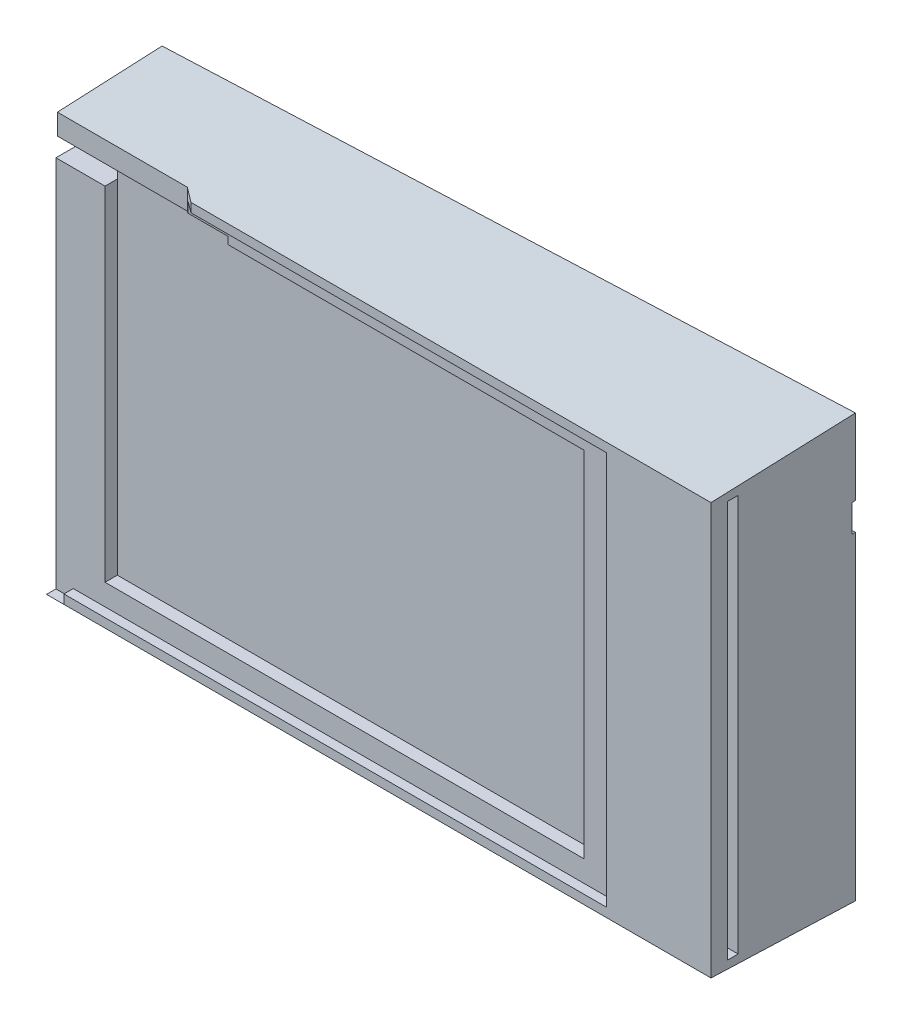
SolidWorks part; units mm, degrees
ref_plane "Front Plane" through (0, 0, 0) normal (0, 0, 1) x (1, 0, 0)
ref_plane "Top Plane" through (0, 0, 0) normal (0, 1, 0) x (1, 0, 0)
ref_plane "Right Plane" through (0, 0, 0) normal (1, 0, 0) x (0, 0, -1)
sketch "Sketch1" plane through (0, 0, 0) normal (0, 0, 1) x (1, 0, 0)
  line L1 (0, 0) -> (92, 0)
  line L2 (0, 0) -> (0, 61)
  line L3 (0, 61) -> (92, 61)
  line L4 (92, 0) -> (92, 61)
  dimension "D1" = 61
  dimension "D2" = 92
ref_plane "Plane1" through (92, 0, 0) normal (1, 0, 0) x (0, 0, -1)
sketch "Sketch2" plane through (92, 0, 0) normal (1, 0, 0) x (0, 0, -1)
  line L1 (0, 61) -> (20, 61.75)
  line L2 (0, 61) -> (0, 4)
  line L3 (0, 4) -> (20, 3.25)
  line L4 (20, 61.75) -> (20, 3.25)
  dimension "D1" = 20
  dimension "D2" = 57
  dimension "D3" = 58.5
ref_plane "Plane2" through (0, 0, 0) normal (1, 0, 0) x (0, 0, -1)
sketch "Sketch3" plane through (0, 0, 0) normal (1, 0, 0) x (0, 0, -1)
  line L1 (0, 61) -> (16, 61.75)
  line L2 (0, 61) -> (0, 4)
  line L3 (0, 4) -> (16, 3.25)
  line L4 (16, 61.75) -> (16, 3.25)
  dimension "D1" = 16
  dimension "D2" = 58.5
  dimension "D3" = 57
ref_plane "Plane3" through (0, 61, 0) normal (0, 1, 0) x (1, 0, 0)
loft "body" add profiles "Sketch3", "Sketch2" connector at (0, 61.75, -16) connector at (92, 61.75, -20)
sketch "Sketch5" plane through (0, 61, 0) normal (0, 1, 0) x (1, 0, 0)
  line L0 (0, 1.5) -> (18, 1.5)
  line L1 (0, -33.55) -> (0, 33.55) construction
  line L2 (18, 1.5) -> (20, 0)
  line L3 (0, 0) -> (92, 0) construction
  line L4 (0, 1.5) -> (0, 0)
  line L5 (0, 0) -> (20, 0)
  dimension "D1" = 1.5
  dimension "D2" = 20
  dimension "D3" = 2
sketch "Sketch6" plane through (0, 0, 0) normal (0, 0, 1) x (1, 0, 0)
  line L0 (23.8, 57.2) -> (23.8, 58.2)
  line L1 (6.8, 8.2) -> (73.1, 8.2)
  line L2 (6.8, 8.2) -> (6.8, 57.2)
  line L3 (6.8, 57.2) -> (73.1, 57.2)
  line L4 (73.1, 8.2) -> (73.1, 57.2)
  line L5 (6.8, 8.2) -> (73.1, 57.2) construction
  line L6 (6.8, 57.2) -> (73.1, 8.2) construction
  line L7 (23.8, 58.2) -> (6.8, 58.2)
  line L9 (0, 61) -> (92, 61) construction
  line L10 (0, 0) -> (0, 61) construction
  line L11 (6.8, 57.2) -> (6.8, 58.2)
  line L12 (6.8, 58.2) -> (6.8, 57.2)
  point P0 (39.95, 32.7)
  dimension "D1" = 66.3
  dimension "D2" = 49
  dimension "D3" = 1
  dimension "D4" = 17
  dimension "D5" = 3.8
  dimension "D6" = 6.8
extrude "film plane" cut sketch "Sketch6" against normal blind 3 contours L11 L3 L0 L7 | L1 L4 L3 L2 region at (15.3, 57.7, 0) region at (39.95, 32.7, 0)
sketch "Sketch7" plane through (0, 0, 0) normal (0, 0, 1) x (1, 0, 0)
  line L0 (0, 0) -> (0, 61) construction
  line L1 (77.5, 59.75) -> (0, 59.75)
  line L2 (77.5, 59.75) -> (77.5, 5.25)
  line L3 (77.5, 5.25) -> (0, 5.25)
  line L4 (0, 59.75) -> (0, 5.25)
  line L5 (92, 0) -> (92, 61) construction
  line L6 (77.5, 5.25) -> (77.5, 4) construction
  line L7 (0, 4) -> (92, 4) construction
  line L8 (77.5, 59.75) -> (77.5, 61) construction
  line L9 (0, 61) -> (92, 61) construction
  line L10 (2.4, 5.25) -> (2.4, 4)
  line L11 (2.4, 4) -> (0, 4)
  line L12 (0, 4) -> (0, 5.25)
  line M5 (0, 4) -> (92, 4)
  dimension "D1" = 54.5
  dimension "D2" = 14.5
  dimension "D3" = 2.4
extrude "Cut-Extrude2" cut sketch "Sketch7" against normal blind 1.3 contours L10 L3 M5 | L3 L2 L1 L4 region at (1.2, 4.625, 0)
sketch "notch" plane through (0, 0, -1.3) normal (0, 0, 1) x (1, 0, 0)
  line L0 (6.8, 58.2) -> (0, 58.2)
  line L1 (0, 59.75) -> (0, 4) construction
  line L2 (0, 58.2) -> (0, 55.7)
  line L3 (0, 55.7) -> (6.8, 55.7)
  line L4 (6.8, 58.2) -> (6.8, 8.2) construction
  line L5 (6.8, 55.7) -> (6.8, 58.2)
  dimension "D1" = 2.5
extrude "notch-cut" cut sketch "notch" against normal blind 4.1
sketch "Sketch10" plane through (-0.6943, 0, -15.9698) normal (-0.0434, 0, -0.9991) x (-0.9991, 0, 0.0434)
  line L0 (-92.7819, 51.25) -> (-86.4841, 51.25)
  line L1 (-92.7819, 3.25) -> (-92.7819, 61.75) construction
  line L2 (-86.4841, 51.25) -> (-86.4841, 47.45)
  line L3 (-86.4841, 47.45) -> (-92.7819, 47.45)
  line L4 (-92.7819, 47.45) -> (-92.7819, 51.25)
  line L6 (-92.7819, 61.75) -> (-0.695, 61.75) construction
  dimension "D1" = 10.5
  dimension "D2" = 3.8
extrude "Cut-Extrude4" cut sketch "Sketch10" against normal blind 0.5
sketch "Sketch11" plane through (-0.6943, 0, -15.9698) normal (-0.0434, 0, -0.9991) x (-0.9991, 0, 0.0434)
  line L0 (-92.7819, 3.25) -> (-92.7819, 47.45) construction
  line L1 (-72.5, 14.5) -> (-64, 14.5)
  line L2 (-75, 17) -> (-75, 48)
  line L3 (-72.5, 50.5) -> (-64, 50.5)
  line L4 (-61.5, 17) -> (-61.5, 48)
  line L5 (-24.5, 14.5) -> (-16, 14.5)
  line L6 (-27, 17) -> (-27, 48)
  line L7 (-24.5, 50.5) -> (-16, 50.5)
  line L8 (-13.5, 17) -> (-13.5, 48)
  line L11 (-0.695, 32.5) -> (-92.7819, 32.5) construction
  line L12 (-0.695, 3.25) -> (-0.695, 61.75) construction
  line L13 (0, 0) -> (0, 61) construction
  arc A0 (-24.5, 14.5) -> (-27, 17) centre (-24.5, 17) cw
  arc A1 (-16, 14.5) -> (-13.5, 17) centre (-16, 17) ccw
  arc A2 (-16, 50.5) -> (-13.5, 48) centre (-16, 48) cw
  arc A3 (-27, 48) -> (-24.5, 50.5) centre (-24.5, 48) cw
  arc A4 (-75, 48) -> (-72.5, 50.5) centre (-72.5, 48) cw
  arc A5 (-64, 50.5) -> (-61.5, 48) centre (-64, 48) cw
  arc A6 (-64, 14.5) -> (-61.5, 17) centre (-64, 17) ccw
  arc A7 (-72.5, 14.5) -> (-75, 17) centre (-72.5, 17) cw
  point P10 (-13.5, 32.5)
  point P27 (-75, 50.5)
  point P34 (-75, 14.5)
  dimension "D6" = 2.5
  dimension "D1" = 36
  dimension "D3" = 34.5
  dimension "D4" = 13.5
  dimension "D2" = 13.5
  dimension "D5" = 13.5
extrude "Cut-Extrude5" cut sketch "Sketch11" against normal blind 1.5
extrude "Cut-Extrude6" cut sketch "Sketch5" against normal blind 5 and the other way through all
sketch "草图1" plane through (92, 0, 0) normal (1, 0, 0) x (0, 0, -1)
  line L0 (3, 60) -> (3, 5)
  line L1 (0, 61) -> (0, 4) construction
  point P4 (3, 5.3153)
  point P5 (0, 32.5)
  point P6 (3, 32.5)
  dimension "D1" = 3
  dimension "D2" = 55
extrude "outlet" cut sketch "草图1" against normal blind 2 thin thin type mid plane wall 1.5
equation "\"D5@Sketch11\"=\"D2@Sketch11\""
